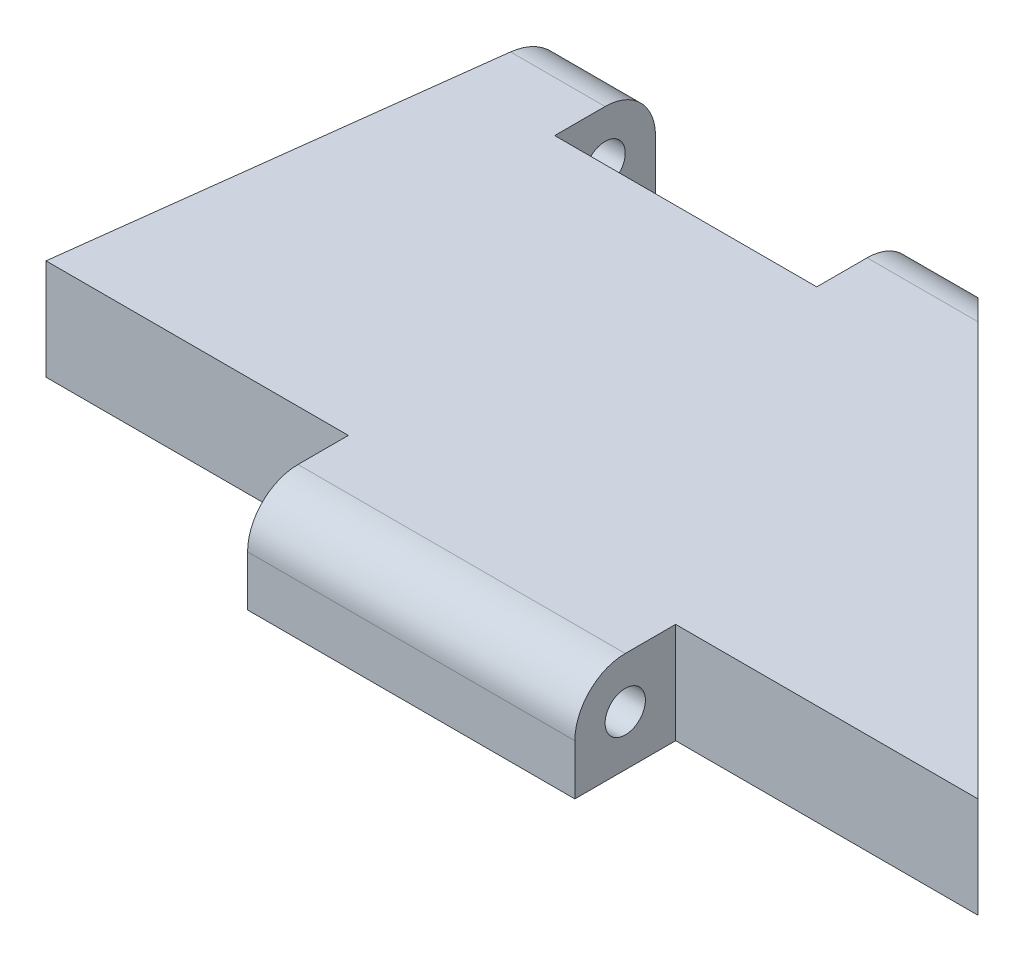
SolidWorks part; units mm, degrees
material "ABS PC"
ref_plane "Front Plane" through (0, 0, 0) normal (0, 0, 1) x (1, 0, 0)
ref_plane "Top Plane" through (0, 0, 0) normal (0, 1, 0) x (1, 0, 0)
ref_plane "Right Plane" through (0, 0, 0) normal (1, 0, 0) x (0, 0, -1)
sketch "Sketch1" plane through (0, 0, 0) normal (0, 1, 0) x (1, 0, 0)
  line L0 (-26.5064, 19.0996) -> (32.214, 19.0996)
  line L1 (32.214, 19.0996) -> (9.354, 41.9596)
  line L2 (9.354, 41.9596) -> (-23.666, 41.9596)
  line L3 (-23.666, 41.9596) -> (-26.5064, 19.0996)
  dimension "D1" = 45
  dimension "D2" = 33.02
  dimension "D3" = 58.7204
  dimension "D4" = 22.86
extrude "Boss-Extrude1" add sketch "Sketch1" along normal blind 6.35
sketch "Sketch2" plane through (0, 0, 0) normal (1, 0, 0) x (0, 0, -1)
  line L0 (19.0996, 6.35) -> (19.0996, 0) construction
  line L2 (12.7496, 0) -> (19.0996, 0)
  line L3 (12.7496, 0) -> (12.7496, 6.35)
  line L4 (12.7496, 6.35) -> (19.0996, 6.35)
  line L5 (19.0996, 0) -> (19.0996, 6.35)
  line L6 (12.7496, 0) -> (19.0996, 6.35) construction
  line L7 (12.7496, 6.35) -> (19.0996, 0) construction
  circle A0 centre (15.9246, 3.175) radius 3.175
  circle A1 centre (15.9246, 3.175) radius 1.27
  point P5 (19.0996, 3.175)
  dimension "D1" = 6.35
  dimension "D4" = 2.54
  dimension "D2" = 3.175
  dimension "D3" = 0
extrude "Boss-Extrude2" add sketch "Sketch2" along normal up to vertex (32.214 mm away) and the other way up to vertex (26.5064 mm away) contours A0 L2 L5 | A0 L5 L4 | A0 A1 | A0 L3 L2 region at (0, 0.7092, -13.4587) region at (0, 0.7092, -18.3904) region at (0, 0.9934, -13.743) region at (0, 5.6408, -18.3904) up to point (32.214, 0, -19.0996) other way up to point (-26.5064, 0, -19.0996)
extrude "Cut-Extrude1" cut sketch "Sketch2<7>" against normal blind 19.05 from surface contours A0 A1 | A0 L2 L5 | A0 L3 L2 | A0 L5 L4 region at (0, 0.7092, -13.4587) region at (0, 0.7092, -18.3904) region at (0, 0.9934, -13.743) region at (0, 5.6408, -18.3904) starting at face at (32.214, 3.3065, -15.793)
sketch "Sketch2<7>" plane through (0, 0, 0) normal (1, 0, 0) x (0, 0, -1) same geometry as "Sketch2"
extrude "Cut-Extrude2" cut sketch "Sketch2<8>" along normal blind 19.05 from surface contours A0 A1 | A0 L2 L5 | A0 L3 L2 | A0 L5 L4 region at (0, 0.7092, -13.4587) region at (0, 0.7092, -18.3904) region at (0, 0.9934, -13.743) region at (0, 5.6408, -18.3904) starting at face at (-26.5064, 3.3065, -15.793)
sketch "Sketch2<8>" plane through (0, 0, 0) normal (1, 0, 0) x (0, 0, -1) same geometry as "Sketch2"
sketch "Sketch5" plane through (0, 0, 0) normal (1, 0, 0) x (0, 0, -1)
  line L0 (41.9596, 6.35) -> (41.9596, 0) construction
  line L1 (19.0996, 6.35) -> (41.9596, 6.35) construction
  line L2 (48.3096, 0) -> (41.9596, 0)
  line L3 (48.3096, 0) -> (48.3096, 6.35)
  line L4 (48.3096, 6.35) -> (41.9596, 6.35)
  line L5 (41.9596, 0) -> (41.9596, 6.35)
  line L6 (48.3096, 0) -> (41.9596, 6.35) construction
  line L7 (48.3096, 6.35) -> (41.9596, 0) construction
  circle A0 centre (45.1346, 3.175) radius 3.175
  circle A1 centre (45.1346, 3.175) radius 1.27
  point P4 (41.9596, 3.175)
  dimension "D3" = 6.35
  dimension "D4" = 2.54
  dimension "D1" = 3.175
  dimension "D2" = 0
  dimension "D5" = 0
extrude "Boss-Extrude3" add sketch "Sketch5" along normal blind 19.05 and the other way blind 24.13 contours A0 L2 L3 | A0 L5 L2 | A0 L4 L5 | A0 A1 | A0 region at (0, 0.7092, -47.6004) region at (0, 0.7092, -42.6687) region at (0, 0.9934, -42.953) region at (0, 5.6408, -42.6687)
sketch "Sketch3" plane through (0, 6.35, 0) normal (0, 1, 0) x (1, 0, 0)
  line L0 (-23.666, 41.9596) -> (-20.0166, 71.3302)
  line L1 (9.354, 41.9596) -> (-20.0166, 71.3302)
  line L2 (-23.666, 41.9596) -> (-26.5064, 19.0996) construction
  line L3 (32.214, 19.0996) -> (9.354, 41.9596) construction
  line L4 (-23.666, 41.9596) -> (-46.5462, 30.9999)
  line L5 (-46.5462, 30.9999) -> (-40.9529, 76.0154)
  line L6 (-40.9529, 76.0154) -> (42.6798, 71.3302)
  line L7 (42.6798, 71.3302) -> (25.5314, 33.8554)
  line L8 (25.5314, 33.8554) -> (9.354, 41.9596)
  dimension "D1" = 180
  dimension "D2" = 180
extrude "Cut-Extrude3" cut sketch "Sketch3" against normal blind 19.05
ref_plane "Plane1" through (3.004, 0, 0) normal (-1, 0, 0) x (0, 1, 0)
sketch "Sketch6" plane through (3.004, 0, 0) normal (-1, 0, 0) x (0, 1, 0)
  line L0 (6.35, 19.0996) -> (6.35, 45.1346) construction
  line L1 (6.35, 41.9596) -> (0, 41.9596)
  line L2 (6.35, 41.9596) -> (6.35, 48.3096)
  line L3 (6.35, 48.3096) -> (0, 48.3096)
  line L4 (0, 41.9596) -> (0, 48.3096)
  line L5 (6.35, 41.9596) -> (0, 48.3096) construction
  line L6 (6.35, 48.3096) -> (0, 41.9596) construction
  circle A0 centre (3.175, 45.1346) radius 3.175
  circle A1 centre (3.175, 45.1346) radius 1.27
  dimension "D2" = 2.54
  dimension "D1" = 0
extrude "Cut-Extrude4" cut sketch "Sketch6" along normal blind 16.51 from offset 3.81 contours A0 A1 | A0 L2 L3 | A0 L3 L4 | A0 L1 L2 | A0 L4 L1 region at (3.004, 5.6408, -42.6687) region at (3.004, 0.7092, -42.6687) region at (3.004, 0.9934, -42.953) region at (3.004, 5.6408, -47.6004) region at (3.004, 0.7092, -47.6004)
extrude "Cut-Extrude5" cut sketch "Sketch6<4>" along normal blind 22.86 contours A1 region at (3.004, 3.175, -45.1346)
sketch "Sketch6<4>" plane through (3.004, 0, 0) normal (-1, 0, 0) x (0, 1, 0) same geometry as "Sketch6"
